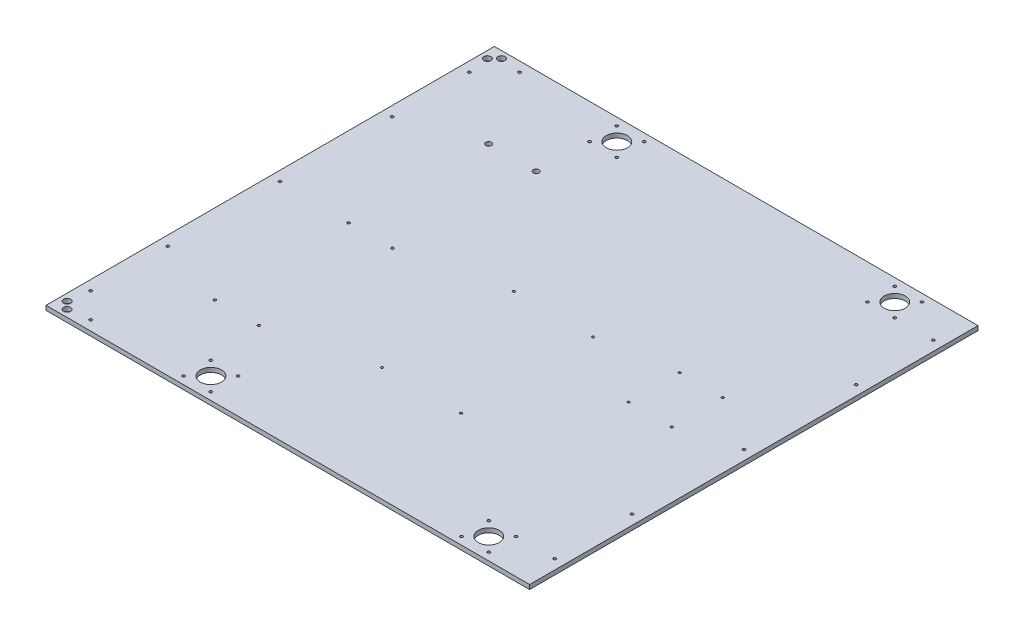
SolidWorks part; units mm, degrees
ref_plane "Front Plane" through (0, 0, 0) normal (0, 0, 1) x (1, 0, 0)
ref_plane "Top Plane" through (0, 0, 0) normal (0, 1, 0) x (1, 0, 0)
ref_plane "Right Plane" through (0, 0, 0) normal (1, 0, 0) x (0, 0, -1)
sketch "Sketch1" plane through (0, 0, 0) normal (1, 0, 0) x (0, 0, -1)
  line L0 (0, 0) -> (-510, 0)
  line L1 (-510, 0) -> (-510, 5)
  line L2 (-510, 5) -> (0, 5)
  line L6 (0, 5) -> (0, 0)
  dimension "D1" = 510
  dimension "D2" = 5
extrude "Boss-Extrude1" add sketch "Sketch1" along normal blind 550
sketch "BotthomHoles-Sketch2" plane through (0, 5, 0) normal (0, 1, 0) x (1, 0, 0)
  line L0 (550, -3.175) -> (0, -3.175) construction
  line L2 (550, 0) -> (550, -510) construction
  line L3 (550, 0) -> (0, 0) construction
  line L4 (550, -510) -> (0, -510) construction
  line L7 (0, 0) -> (0, -510) construction
  line L8 (550, 0) -> (550, -510) construction
  circle A0 centre (479.425, -24.175) radius 12
  circle A2 centre (463.925, -8.675) radius 1.5875
  circle A3 centre (494.925, -8.675) radius 1.5875
  circle A6 centre (463.925, -39.675) radius 1.5875
  circle A7 centre (494.925, -39.675) radius 1.5875
  circle A8 centre (39.6875, -11.1125) radius 1.5875
  circle A10 centre (178.925, -39.675) radius 1.5875
  circle A11 centre (147.925, -39.675) radius 1.5875
  circle A12 centre (178.925, -8.675) radius 1.5875
  circle A13 centre (147.925, -8.675) radius 1.5875
  circle A14 centre (163.425, -24.175) radius 12
  circle A15 centre (39.6875, -498.8875) radius 1.5875
  circle A16 centre (147.925, -501.325) radius 1.5875
  circle A17 centre (178.925, -501.325) radius 1.5875
  circle A18 centre (147.925, -470.325) radius 1.5875
  circle A19 centre (178.925, -470.325) radius 1.5875
  circle A20 centre (463.925, -470.325) radius 1.5875
  circle A21 centre (463.925, -501.325) radius 1.5875
  circle A22 centre (494.925, -470.325) radius 1.5875
  circle A23 centre (494.925, -501.325) radius 1.5875
  circle A25 centre (163.425, -485.825) radius 12
  circle A26 centre (479.425, -485.825) radius 12
  circle A27 centre (11.1125, -39.6875) radius 1.5875
  circle A28 centre (11.1125, -127.5) radius 1.5875
  circle A29 centre (11.1125, -255) radius 1.5875
  circle A30 centre (11.1125, -382.5) radius 1.5875
  circle A31 centre (11.1125, -470.3125) radius 1.5875
  circle A32 centre (538.8875, -470.3125) radius 1.5875
  circle A33 centre (538.8875, -382.5) radius 1.5875
  circle A34 centre (538.8875, -255) radius 1.5875
  circle A35 centre (538.8875, -127.5) radius 1.5875
  circle A36 centre (538.8875, -39.6875) radius 1.5875
  dimension "D9" = 3.175
  dimension "D10" = 24
  dimension "D13" = 3.175
  dimension "D29" = 3.175
  dimension "D2" = 8.675
  dimension "D5" = 15.5
  dimension "D6" = 31
  dimension "D7" = 15.5
  dimension "D8" = 31
  dimension "D11" = 21
  dimension "D12" = 39.6875
  dimension "D15" = 31
  dimension "D16" = 15.5
  dimension "D17" = 316
  dimension "D3" = 70.575
  dimension "D4" = 11.1125
  dimension "D18" = 8.675
  dimension "D19" = 15.5
  dimension "D20" = 31
  dimension "D21" = 11.1125
  dimension "D22" = 39.6875
  dimension "D23" = 39.6875
  dimension "D24" = 127.5
  dimension "D25" = 127.5
  dimension "D26" = 127.5
  dimension "D27" = 11.1125
  dimension "D28" = 11.1125
  dimension "D14" = 163.425
extrude "BottomEnclosureHoles-Cut-Extrude1" cut sketch "BotthomHoles-Sketch2" against normal through all
sketch "BottomPSUHolesSketch2" plane through (0, 5, 0) normal (0, 1, 0) x (1, 0, 0)
  line L0 (0, 0) -> (0, -510) construction
  line L3 (550, 0) -> (0, 0) construction
  line L4 (550, -510) -> (0, -510) construction
  circle A0 centre (90.8, -256.7) radius 1.5
  circle A1 centre (140.8, -256.7) radius 1.5
  circle A2 centre (90.8, -408.7) radius 1.5
  circle A3 centre (140.8, -408.7) radius 1.5
  circle A6 centre (92.8, -99.3) radius 3.25
  circle A7 centre (146.8, -99.3) radius 3.25
  dimension "D6" = 3
  dimension "D4" = 6.5
  dimension "D1" = 152
  dimension "D2" = 50
  dimension "D3" = 90.8
  dimension "D7" = 54
  dimension "D8" = 2
  dimension "D9" = 99.3
  dimension "D5" = 101.3
extrude "BottomPSUHolesCut-Extrude1" cut sketch "BottomPSUHolesSketch2" against normal through all
sketch "RPIHolesSketch2" plane through (0, 5, 0) normal (0, 1, 0) x (1, 0, 0)
  line L0 (550, 0) -> (0, 0) construction
  line L1 (0, 0) -> (0, -510) construction
  line L2 (550, 0) -> (550, -510) construction
  line L3 (550, -510) -> (0, -510) construction
  circle A4 centre (426.7, -216) radius 1.35
  circle A5 centre (475.7, -216) radius 1.35
  circle A6 centre (426.7, -274) radius 1.35
  circle A7 centre (475.7, -274) radius 1.35
  dimension "D7" = 2.7
  dimension "D4" = 58
  dimension "D5" = 49
  dimension "D8" = 216
  dimension "D10" = 74.3
  dimension "D11" = 236
  dimension "D2" = 426.7
extrude "RPIHolesCut-Extrude1" cut sketch "RPIHolesSketch2" against normal through all
sketch "CableHolesSketch2" plane through (0, 5, 0) normal (0, 1, 0) x (1, 0, 0)
  line L0 (550, 0) -> (0, 0) construction
  line L1 (550, -510) -> (0, -510) construction
  line L2 (0, 0) -> (0, -510) construction
  circle A0 centre (8, -494) radius 4
  circle A1 centre (16, -502) radius 4
  circle A2 centre (8, -16) radius 4
  circle A3 centre (16, -8) radius 4
  dimension "D6" = 8
  dimension "D1" = 16
  dimension "D2" = 16
  dimension "D3" = 16
  dimension "D4" = 8
  dimension "D5" = 8
  dimension "D7" = 8
extrude "CableHolesCut-Extrude1" cut sketch "CableHolesSketch2" against normal through all
sketch "OctopusHolesSketch2" plane through (0, 5, 0) normal (0, 1, 0) x (1, 0, 0)
  line L0 (0, 0) -> (0, -510) construction
  circle A0 centre (252.3, -230.2) radius 1.35
  circle A1 centre (252.3, -380.2) radius 1.35
  circle A2 centre (342.3, -230.2) radius 1.35
  circle A3 centre (342.3, -380.2) radius 1.35
  point P13 (0, 0)
  dimension "D3" = 2.7
  dimension "D1" = 150
  dimension "D2" = 90
  dimension "D4" = 111.5
  dimension "D5" = 26.5
  dimension "D6" = 252.3
  dimension "D7" = 129.8
extrude "OctopusHolesCut-Extrude1" cut sketch "OctopusHolesSketch2" against normal through all
equation "\"LowerRailWidth\"= 2.00in"
equation "\"RailThickness\"= .125in'Spec"
equation "\"StepperHoleDiameter\"= 24mm"
equation "\"StepperMountingHoleDiameter\"= 3.175mm"
equation "\"SideRailLength\"= 550mm"
equation "\"StepperMountingHoleDistance\"= 31mm'Spec"
equation "\"StepperMountingHoleOffsetFromLeftOrRightSide\"= \"StepperMountingHoleOffsetFromItsSide\" + \"RailThickness\""
equation "\"HoleOffsetFromEdge\"= \"RailThickness\" * 2.5"
equation "\"HoleOffsetFromSide\"= \"RailThickness\" * 3.5"
equation "\"StepperMountingHoleOffsetFromItsSide\"= 5.5mm'Spec"
equation "\"FasteningHoleDiameter\"= .125in"
equation "\"D2@BotthomHoles-Sketch2\" = \"StepperMountingHoleOffsetFromLeftOrRightSide\""
equation "\"D5@BotthomHoles-Sketch2\" = \"StepperMountingHoleDistance\" / 2"
equation "\"D6@BotthomHoles-Sketch2\" = \"StepperMountingHoleDistance\""
equation "\"D7@BotthomHoles-Sketch2\" = \"StepperMountingHoleDistance\" / 2"
equation "\"D8@BotthomHoles-Sketch2\" = \"StepperMountingHoleDistance\""
equation "\"D9@BotthomHoles-Sketch2\" = \"StepperMountingHoleDiameter\""
equation "\"D10@BotthomHoles-Sketch2\" = \"StepperHoleDiameter\""
equation "\"D1@Boss-Extrude1\"=\"SideRailLength\""
equation "\"BedThirdSize\"= 70mm"
equation "\"BedInnerSquareWidth\"= \"BedThirdSize\" * 3'Equals 210"
equation "\"BedInnerSquareLength\"= \"BedInnerSquareWidth\""
equation "\"BedLWidth\"= \"BedThirdSize\"'Equals 70"
equation "\"BedLength\"= \"BedInnerSquareLength\" + \"BedLWidth\" * 2 + \"BedIncreasedByLength\"'Equals 350"
equation "\"DistanceBetweenFrontToBackStepperHoles\"= \"BedLength\" - \"DistanceFromBedFrontToFirstLeftStepperHole\"'Equals 316"
equation "\"DistanceFromBedFrontToFirstLeftStepperHole\"= \"LeadScrewNutPadSize\" + 10mm'Equals 34"
equation "\"DistanceFromFrontSideToBedFront\"= \"RailThickness\" + \"BeltTensionerDepth\" + 10mm'Equals 36.575"
equation "\"20TGT2PulleyDiameter\"= 17.9mm'Spec"
equation "\"BeltTensionerBackWallThickness\"= 4mm"
equation "\"BeltTensionerSpaceBetweenPulleyAndWall\"= 1.5mm"
equation "\"BeltTensionerInnerDepth\"= \"20TGT2PulleyDiameter\" + \"BeltTensionerSpaceBetweenPulleyAndWall\""
equation "\"BeltTensionerDepth\"= \"BeltTensionerBackWallThickness\" + \"BeltTensionerInnerDepth\"'Equals 23.4"
equation "\"BedIncreasedByLength\"= 0mm"
equation "\"LowerCornerBlockWidth\"= \"LowerRailWidth\" - \"RailThickness\" * 2'Room for left front stepper"
equation "\"D12@BotthomHoles-Sketch2\"=\"CornerEnclosureOffset\""
equation "\"D13@BotthomHoles-Sketch2\"=\"FasteningHoleDiameter\""
equation "\"CornerEnclosureOffset\"= \"LowerCornerBlockWidth\" - \"HoleOffsetFromEdge\" + \"RailThickness\""
equation "\"LowerCornerBlockY1FromSide\"= \"HoleOffsetFromSide\""
equation "\"D15@BotthomHoles-Sketch2\"=\"StepperMountingHoleDistance\""
equation "\"D16@BotthomHoles-Sketch2\"=\"StepperMountingHoleDistance\"/2"
equation "\"D17@BotthomHoles-Sketch2\"=\"DistanceBetweenFrontToBackStepperHoles\""
equation "\"DistanceFromFrontSideToFirstLeftStepperHole\"= \"DistanceFromFrontSideToBedFront\" + \"DistanceFromBedFrontToFirstLeftStepperHole\"'Equals 70.575"
equation "\"LeadScrewNutMountingHoleFlangeDiameter\"= 22mm'Spec"
equation "\"LeadScrewNutPadSize\"= \"LeadScrewNutMountingHoleFlangeDiameter\" + 2mm'Equals 24"
equation "\"D3@BotthomHoles-Sketch2\"=\"DistanceFromFrontSideToFirstLeftStepperHole\""
equation "\"LowerEnclosureThickness\"= 5mm"
equation "\"FrontBackRailLength\"= 510mm"
equation "\"D4@BotthomHoles-Sketch2\"=\"LowerCornerBlockY1FromSide\""
equation "\"D1@Sketch1\"=\"FrontBackRailLength\""
equation "\"D18@BotthomHoles-Sketch2\"=\"StepperMountingHoleOffsetFromLeftOrRightSide\""
equation "\"D19@BotthomHoles-Sketch2\"=\"StepperMountingHoleDistance\"/2"
equation "\"D20@BotthomHoles-Sketch2\"=\"StepperMountingHoleDistance\""
equation "\"D21@BotthomHoles-Sketch2\"=\"LowerCornerBlockY1FromSide\""
equation "\"D22@BotthomHoles-Sketch2\"=\"CornerEnclosureOffset\""
equation "\"D23@BotthomHoles-Sketch2\"=\"CornerEnclosureOffset\""
equation "\"FrontOrBackEnclosureOffsets\"= \"FrontBackRailLength\" / 4"
equation "\"D24@BotthomHoles-Sketch2\"=\"FrontOrBackEnclosureOffsets\""
equation "\"D25@BotthomHoles-Sketch2\"=\"FrontOrBackEnclosureOffsets\""
equation "\"D26@BotthomHoles-Sketch2\"=\"FrontOrBackEnclosureOffsets\""
equation "\"D27@BotthomHoles-Sketch2\"=\"LowerCornerBlockY1FromSide\""
equation "\"D28@BotthomHoles-Sketch2\"=\"LowerCornerBlockY1FromSide\""
equation "\"D29@BotthomHoles-Sketch2\"=\"FasteningHoleDiameter\""
equation "\"D2@Sketch1\"=\"LowerEnclosureThickness\""
equation "\"24VPSUMountingHolesShortDistanceBetween\"= 50mm'Yours may differ"
equation "\"24VPSUMountingHolesLongDistanceBetween\"= 152mm'Yours may differ"
equation "\"24VPSUMountingHoleOffsetFromEitherSide\"= 30mm'Yours may differ"
equation "\"24VPSUMountingHoleOffsetFromEdge\"= \"24VPSUMountingHoleOffsetFromEitherSide\" + \"LowerRailWidth\" + 10mm'Yours may differ"
equation "\"24VPSUMountingHoleDiameter\"= 3mm'Yours may differ"
equation "\"D2@BottomPSUHolesSketch2\" = \"24VPSUMountingHolesShortDistanceBetween\""
equation "\"D1@BottomPSUHolesSketch2\" = \"24VPSUMountingHolesLongDistanceBetween\""
equation "\"D3@BottomPSUHolesSketch2\" = \"24VPSUMountingHoleOffsetFromEdge\""
equation "\"D6@BottomPSUHolesSketch2\" = \"24VPSUMountingHoleDiameter\""
equation "\"RPi4BoardLength\"= 85mm'Spec"
equation "\"RPi4BoardWidth\"= 56mm'Spec"
equation "\"RPi4BoardMountingHoleOffsetFromEdge\"= 3.5mm'Spec"
equation "\"RPi4BoardMountingHoleDiameter\"= 2.7mm'Spec"
equation "\"OctopusV1.1BoardMountingHoleOffsetFromAllEdges\"= 3.5mm'Spec"
equation "\"OctopusV1.1BoardMountingHoleLengthDistanceBetween\"= 150mm'Spec"
equation "\"OctopusV1.1BoardMountingHoleWidthDistanceBetween\"= 90mm'Spec"
equation "\"D4@RPIHolesSketch2\" = \"RPi4BoardMountingHoleLengthDistanceBetween\""
equation "\"D5@RPIHolesSketch2\" = \"RPi4BoardWidth\" - \"RPi4BoardMountingHoleOffsetFromEdge\" * 2"
equation "\"D7@RPIHolesSketch2\" = \"RPi4BoardMountingHoleDiameter\""
equation "\"RPi4BoardMountingHoleLengthDistanceBetween\"= 58mm'Spec"
equation "\"OctopusV1.1BoardMountingHoleDiameter\"= 2.7mm'Spec"
equation "\"D8@RPIHolesSketch2\" =  ( \"FrontBackRailLength\" - \"RPi4BoardLength\" )  / 2 + \"RPi4BoardMountingHoleOffsetFromEdge\""
equation "\"D10@RPIHolesSketch2\" = \"LowerRailWidth\" + \"RPi4BoardMountingHoleOffsetFromEdge\" + \"EnclosurePartsOffsetFromFrameInnerEdge\""
equation "\"RCNUN5VMountingHoleDiameter\"= 6.5mm'Spec"
equation "\"RCNUN5VHeight\"= 57mm'Spec"
equation "\"RCNUN5VMountingHoleWidthDistance\"= 54mm'Spec. STL Is incorrect?"
equation "\"D7@BottomPSUHolesSketch2\"=\"RCNUN5VMountingHoleWidthDistance\""
equation "\"D8@BottomPSUHolesSketch2\"=(\"RCNUN5VMountingHoleWidthDistance\" - \"24VPSUMountingHolesShortDistanceBetween\")/2"
equation "\"D9@BottomPSUHolesSketch2\"=\"LowerRailWidth\" + \"RCNUN5VHeight\"/2 + \"EnclosurePartsOffsetFromFrameInnerEdge\""
equation "\"EnclosurePartsOffsetFromFrameInnerEdge\"= 20mm"
equation "\"D5@BottomPSUHolesSketch2\"= \"LowerRailWidth\" + \"EnclosurePartsOffsetFromFrameInnerEdge\" + ( \"24VPSULength\" - \"24VPSUMountingHolesLongDistanceBetween\" ) / 2"
equation "\"24VPSULength\"= 213mm'Spec"
equation "\"LowerRailCableHoleDiameter\"= 8mm"
equation "\"LowerRailCableHoleOffsetFromSide\"= 8mm"
equation "\"LowerRailCableHoleOffsetFromEdge\"= 16mm"
equation "\"D1@CableHolesSketch2\"=\"LowerRailCableHoleOffsetFromEdge\""
equation "\"D2@CableHolesSketch2\"=\"LowerRailCableHoleOffsetFromEdge\""
equation "\"D3@CableHolesSketch2\"=\"LowerRailCableHoleOffsetFromEdge\""
equation "\"D4@CableHolesSketch2\"=\"LowerRailCableHoleOffsetFromSide\""
equation "\"D5@CableHolesSketch2\"=\"LowerRailCableHoleOffsetFromSide\""
equation "\"D6@CableHolesSketch2\"=\"LowerRailCableHoleDiameter\""
equation "\"D7@CableHolesSketch2\"=\"LowerRailCableHoleOffsetFromSide\""
equation "\"D1@OctopusHolesSketch2\"=\"OctopusV1.1BoardMountingHoleLengthDistanceBetween\""
equation "\"D2@OctopusHolesSketch2\"=\"OctopusV1.1BoardMountingHoleWidthDistanceBetween\""
equation "\"D3@OctopusHolesSketch2\"=\"OctopusV1.1BoardMountingHoleDiameter\""
equation "\"24VPSUMountingHoleOffsetFromFront\"= 30mm"
equation "\"D5@OctopusHolesSketch2\"=\"24VPSUMountingHoleOffsetFromFront\" - \"OctopusV1.1BoardMountingHoleOffsetFromAllEdges\""
equation "\"DistanceBetween24VPSUAndOctopus\"= \"24VPSUMountingHoleOffsetFromEitherSide\" + \"OctopusV1.1BoardMountingHoleOffsetFromAllEdges\" + 78'78mm gave me a nice distance to print a cable guide"
equation "\"D4@OctopusHolesSketch2\"=\"DistanceBetween24VPSUAndOctopus\""
